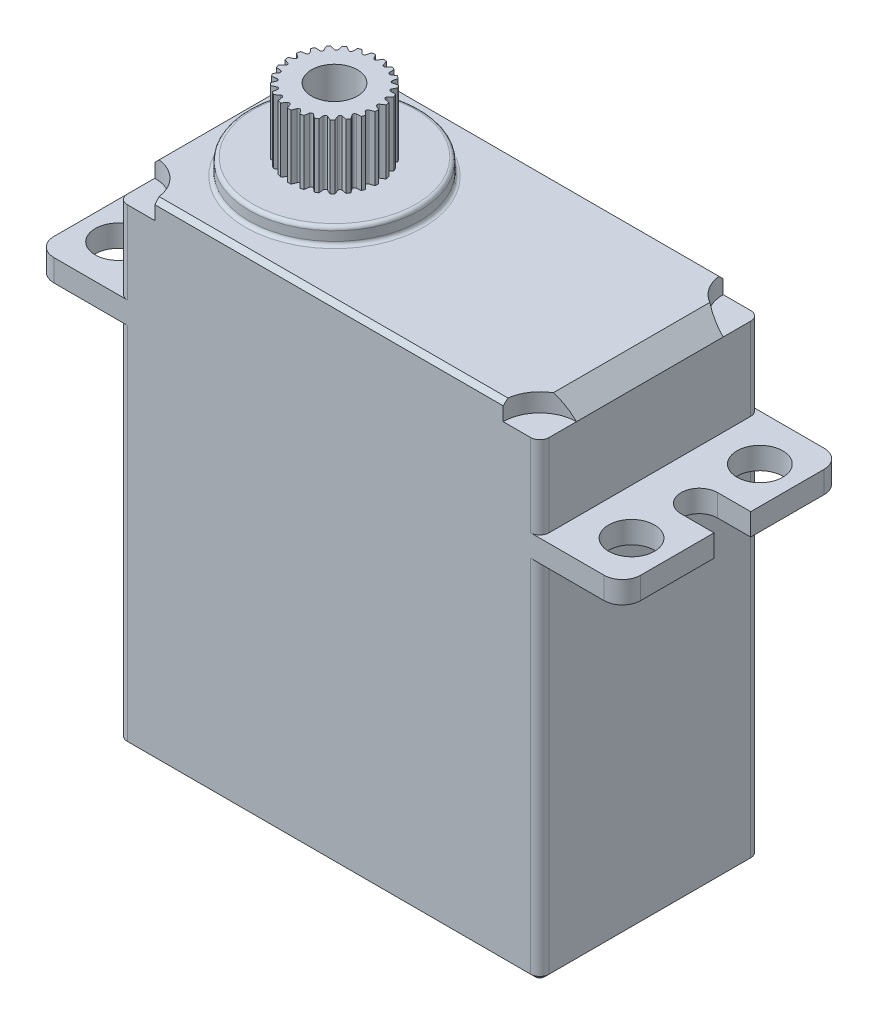
SolidWorks part; units mm, degrees
note: The reader was unsure of these and kept them because the rebuilt part matched: shared geometry of "Sketch3<3>", "Sketch3<4>".
material "1060-O (SS)"
ref_plane "Front Plane" through (0, 0, 0) normal (0, 0, 1) x (1, 0, 0)
ref_plane "Top Plane" through (0, 0, 0) normal (0, 1, 0) x (1, 0, 0)
ref_plane "Right Plane" through (0, 0, 0) normal (1, 0, 0) x (0, 0, -1)
sketch "Sketch1" plane through (0, 0, 0) normal (0, 1, 0) x (1, 0, 0)
  line L1 (-11.0424, 5.8263) -> (11.9576, 5.8263)
  line L2 (-11.0424, 5.8263) -> (-11.0424, -6.1737)
  line L3 (-11.0424, -6.1737) -> (11.9576, -6.1737)
  line L4 (11.9576, 5.8263) -> (11.9576, -6.1737)
  dimension "D1" = 23
  dimension "D2" = 12
extrude "Boss-Extrude1" add sketch "Sketch1" along normal blind 26.6
sketch "Sketch2" plane through (0, 26.6, 0) normal (0, 1, 0) x (1, 0, 0)
  line L0 (-11.0424, -0.1737) -> (11.9576, -0.1737) construction
  line L1 (-11.0424, 5.8263) -> (-11.0424, -6.1737) construction
  line L2 (11.9576, -6.1737) -> (11.9576, 5.8263) construction
  circle A0 centre (-5.2424, -0.1737) radius 4.65
  point P6 (-5.2424, -0.1737)
  point P9 (0, 0)
  dimension "D2" = 9.3
  dimension "D1" = 5.8
extrude "Boss-Extrude2" add sketch "Sketch2" along normal blind 0.9
fillet "Fillet1" radius 0.2 2 edges at (-5.2424, 26.6, 4.8237) (-5.2424, 27.5, 4.8237)
sketch "Sketch3" plane through (0, 27.5, 0) normal (0, 1, 0) x (1, 0, 0)
  line L0 (-5.2424, -0.1737) -> (-5.2424, 2.2963) construction
  line L1 (-5.2424, 1.9143) -> (-5.4576, 2.2869)
  line L2 (-5.2424, 1.9143) -> (-5.0273, 2.2869)
  circle A0 centre (-5.2424, -0.1737) radius 2.47
  circle A1 centre (-5.2424, -0.1737) radius 2.125
  arc A2 (-5.329, 2.0643) -> (-5.1558, 2.0643) centre (-5.2424, 2.1143) ccw
  point P0 (-5.2424, -0.1737)
  dimension "D1" = 4.94
  dimension "D2" = 4.25
  dimension "D5" = 0.1
  dimension "D4" = 2.088
  dimension "D3" = 30
extrude "Boss-Extrude3" add sketch "Sketch3" along normal blind 3.5
sketch "Sketch4" plane through (0, 31, 0) normal (0, 1, 0) x (1, 0, 0)
  circle A0 centre (-5.2424, -0.1737) radius 1.25
  circle A1 centre (-5.2424, -0.1737) radius 2.125 construction
  circle A2 centre (-5.2424, -0.1737) radius 2.125 construction
  dimension "D1" = 2.5
extrude "Cut-Extrude1" cut sketch "Sketch4" against normal blind 3.5
extrude "Boss-Extrude5" add sketch "Sketch3<3>" along normal up to surface (3.5 mm away)
sketch "Sketch3<3>" plane through (0, 27.5, 0) normal (0, 1, 0) x (1, 0, 0) same geometry as "Sketch3"
extrude "Cut-Extrude3" cut sketch "Sketch3<4>" along normal up to surface (3.5 mm away)
sketch "Sketch3<4>" plane through (0, 27.5, 0) normal (0, 1, 0) x (1, 0, 0) same geometry as "Sketch3"
pattern_circular "CirPattern1" count 25 over 360 about axis through (-5.2424, 0, 0.1737) along (0, 1, 0) of "Cut-Extrude3"
ref_plane "Plane1" through (0, 21.1, 0) normal (0, 1, 0) x (1, 0, 0)
sketch "Sketch5" plane through (0, 21.1, 0) normal (0, 1, 0) x (1, 0, 0)
  line L0 (-11.0424, 5.8263) -> (-11.0424, -6.1737) construction
  line L1 (0.4576, 5.8263) -> (0.4576, -6.1737) construction
  line L2 (-15.5424, 4.8263) -> (-15.5424, 0.8263)
  line L3 (11.9576, 5.8263) -> (-11.0424, 5.8263) construction
  line L4 (-11.0424, -6.1737) -> (11.9576, -6.1737) construction
  line L5 (-14.5424, 5.8263) -> (15.4576, 5.8263)
  line L6 (-14.5424, -6.1737) -> (15.4576, -6.1737)
  line L7 (-15.0424, -0.1737) -> (-11.0424, -0.1737) construction
  line L8 (-15.5424, 0.8263) -> (-13.7424, 0.8263)
  line L9 (15.9576, -0.1737) -> (11.9576, -0.1737) construction
  line L10 (-15.5424, -1.1737) -> (-13.7424, -1.1737)
  line L11 (-15.5424, -1.1737) -> (-15.5424, -5.1737)
  line L12 (16.4576, -1.1737) -> (16.4576, -5.1737)
  line L13 (16.4576, -1.1737) -> (14.6576, -1.1737)
  line L14 (16.4576, 0.8263) -> (14.6576, 0.8263)
  line L15 (16.4576, 4.8263) -> (16.4576, 0.8263)
  arc A0 (-15.5424, -5.1737) -> (-14.5424, -6.1737) centre (-14.5424, -5.1737) ccw
  arc A1 (-15.5424, 4.8263) -> (-14.5424, 5.8263) centre (-14.5424, 4.8263) cw
  arc A2 (-13.7424, -1.1737) -> (-13.7424, 0.8263) centre (-13.7424, -0.1737) ccw
  circle A3 centre (-13.5424, 3.3263) radius 1.25
  circle A5 centre (-5.2424, -0.1737) radius 1.25 construction
  circle A6 centre (-13.5424, -3.6737) radius 1.25
  arc A7 (14.6576, -1.1737) -> (14.6576, 0.8263) centre (14.6576, -0.1737) cw
  arc A8 (16.4576, 4.8263) -> (15.4576, 5.8263) centre (15.4576, 4.8263) ccw
  arc A9 (16.4576, -5.1737) -> (15.4576, -6.1737) centre (15.4576, -5.1737) cw
  circle A10 centre (14.4576, -3.6737) radius 1.25
  circle A11 centre (14.4576, 3.3263) radius 1.25
  circle A12 centre (-5.2424, -0.1737) radius 1.25 construction
  point P20 (-12.0424, -0.1737)
  point P43 (12.9576, -0.1737)
  dimension "D2" = 1
  dimension "D3" = 3.5
  dimension "D1" = 8.3
  dimension "D6" = 2.5
  dimension "D4" = 1
  dimension "D5" = 16
  dimension "D7" = 1.8
extrude "Boss-Extrude4" add sketch "Sketch5" against normal blind 1.2
fillet "Fillet2" radius 0.5 4 edges at (11.9576, 23.85, -5.8263) (11.9576, 23.85, 6.1737) (-11.0424, 23.85, -5.8263) (-11.0424, 23.85, 6.1737)
sketch "Sketch6" plane through (0, 26.6, 0) normal (0, 1, 0) x (1, 0, 0)
  line L0 (0.4576, 5.8263) -> (0.4576, -6.1737) construction
  line L1 (11.4576, 5.8263) -> (-10.5424, 5.8263) construction
  line L2 (-10.5424, -6.1737) -> (11.4576, -6.1737) construction
  line L3 (11.9576, -0.1737) -> (-11.0424, -0.1737) construction
  line L4 (11.9576, -5.6737) -> (11.9576, 5.3263) construction
  line L5 (-11.0424, 5.3263) -> (-11.0424, -5.6737) construction
  line L6 (-10.317, 5.8263) -> (-11.0424, 5.8263) construction
  line L7 (-11.0424, 4.91) -> (-11.0424, 5.8263) construction
  circle A0 centre (-11.0424, 5.8263) radius 2
  circle A1 centre (11.9576, 5.8263) radius 2
  circle A2 centre (11.9576, -6.1737) radius 2
  circle A3 centre (-11.0424, -6.1737) radius 2
extrude "Cut-Extrude2" cut sketch "Sketch6" against normal blind 1
chamfer "Chamfer2" distance 1 angle 45 1 edges at (11.9576, 26.6, 0.1737)
fillet "Fillet3" radius 0.5 4 edges at (-11.0424, 9.95, 6.1737) (11.9576, 9.95, -5.8263) (11.9576, 9.95, 6.1737) (-11.0424, 9.95, -5.8263)
chamfer "Chamfer3" distance 0.25 angle 45 11 edges at (0.4576, 0, -5.8263) (-11.0424, 0, 0.1737) (11.9576, 0, 0.1737) (0.4576, 0, 6.1737) (0.4576, 26.6, -5.8263) (0.4576, 26.6, 6.1737) (-11.0424, 26.6, 0.1737) (-10.896, 0, -5.6798) (11.8111, 0, -5.6798) (-10.896, 0, 6.0273) (11.8111, 0, 6.0273)
